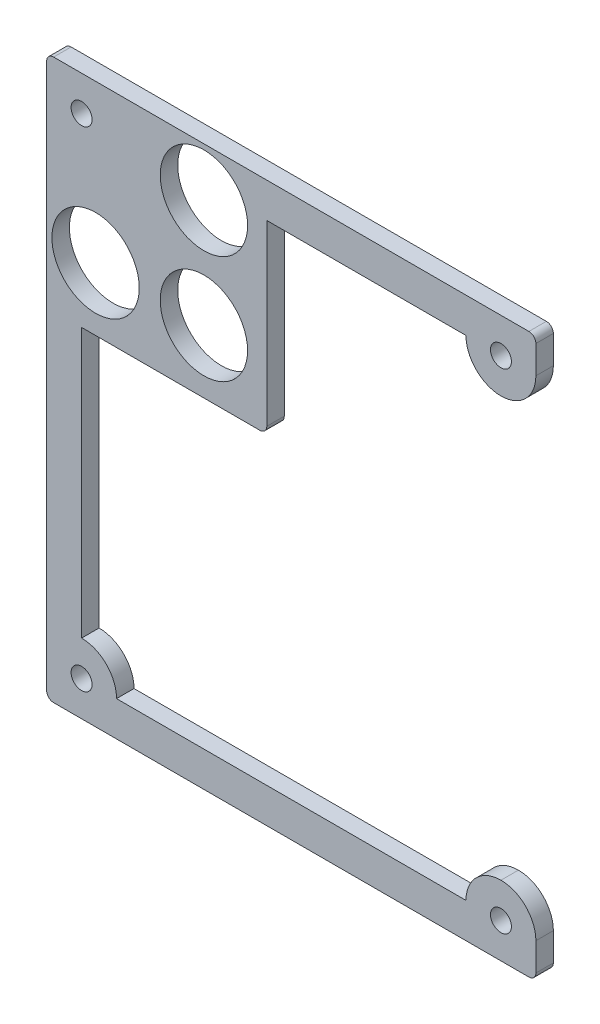
SolidWorks part; units mm, degrees
ref_plane "Front Plane" through (0, 0, 0) normal (0, 0, 1) x (1, 0, 0)
ref_plane "Top Plane" through (0, 0, 0) normal (0, 1, 0) x (1, 0, 0)
ref_plane "Right Plane" through (0, 0, 0) normal (1, 0, 0) x (0, 0, -1)
sketch "Model" plane through (0, 0, 0) normal (0, 0, 1) x (1, 0, 0)
  line L0 (140, 140) -> (140, 158)
  line L1 (140, 20) -> (140, 2)
  line L2 (120, 150) -> (63, 150)
  line L3 (63, 150) -> (63, 99)
  line L4 (61, 97) -> (10, 97)
  line L5 (10, 97) -> (10, 20)
  line L6 (20, 10) -> (120, 10)
  line L11 (2, 0) -> (138, 0)
  line L12 (0, 158) -> (0, 2)
  line L13 (138, 160) -> (2, 160)
  line L14 (130, 20) -> (140, 20)
  line L16 (140, 140) -> (130, 140)
  circle A2 centre (14, 115) radius 12.5
  circle A3 centre (45, 115) radius 12.5
  circle A4 centre (45, 146) radius 12.5
  circle A5 centre (10, 10) radius 3
  circle A6 centre (130, 10) radius 3
  circle A7 centre (130, 150) radius 3
  circle A8 centre (10, 150) radius 3
  arc A10 (120, 150) -> (130, 140) centre (130, 150) ccw
  arc A11 (61, 97) -> (63, 99) centre (61, 99) ccw
  arc A12 (20, 10) -> (10, 20) centre (10, 10) ccw
  arc A13 (130, 20) -> (120, 10) centre (130, 10) ccw
  arc A15 (140, 158) -> (138, 160) centre (138, 158) ccw
  arc A16 (138, 0) -> (140, 2) centre (138, 2) ccw
  arc A17 (0, 2) -> (2, 0) centre (2, 2) ccw
  arc A18 (2, 160) -> (0, 158) centre (2, 158) ccw
extrude "Boss-Extrude2" add sketch "Model" along normal blind 5
fillet "Fillet1" radius 10 1 edges at (140, 20, 2.5)
ref_plane "Plane1" through (140, 140, 5) normal (0, 0, -1) x (-1, 0, 0)
fillet "Fillet2" radius 10 1 edges at (140, 140, 2.5)
